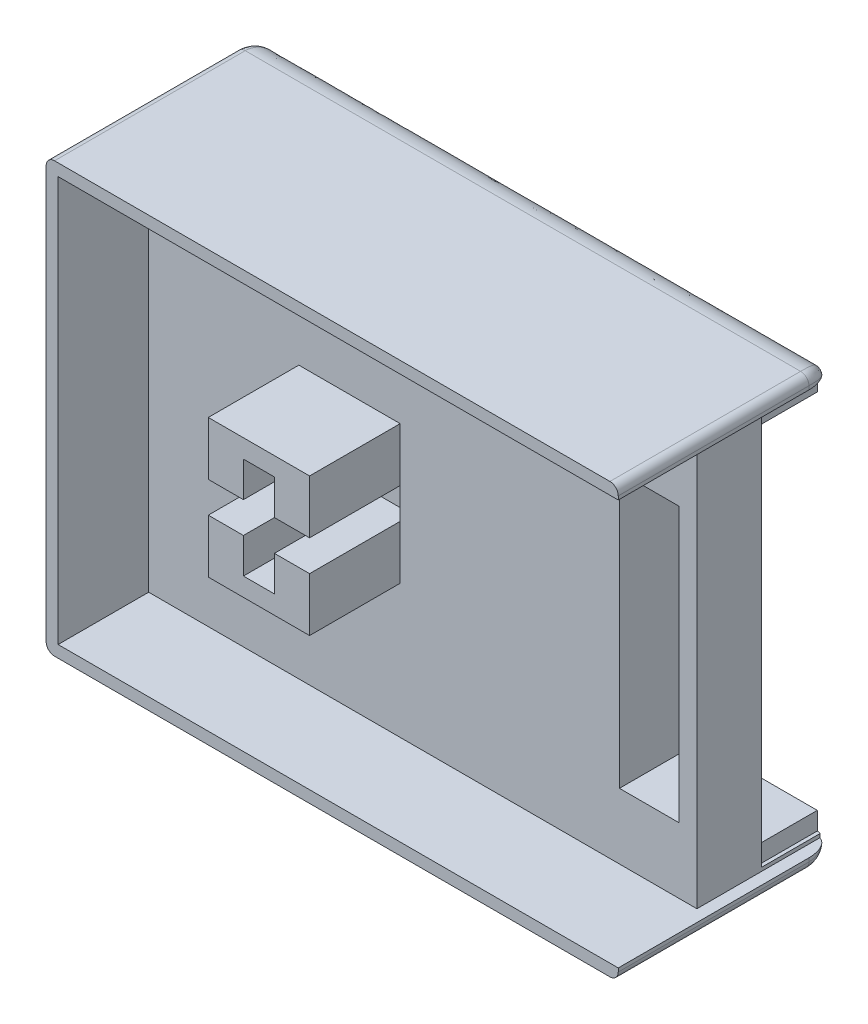
SolidWorks part; units mm, degrees
ref_plane "Front Plane" through (0, 0, 0) normal (0, 0, 1) x (1, 0, 0)
ref_plane "Top Plane" through (0, 0, 0) normal (0, 1, 0) x (1, 0, 0)
ref_plane "Right Plane" through (0, 0, 0) normal (1, 0, 0) x (0, 0, -1)
sketch "Sketch1" plane through (0, 0, 0) normal (0, 0, 1) x (1, 0, 0)
  line L1 (-12, -9) -> (12, -9)
  line L2 (-12, -9) -> (-12, 9)
  line L3 (-12, 9) -> (12, 9)
  line L4 (12, -9) -> (12, 9)
  line L5 (-12, -9) -> (12, 9) construction
  line L6 (-12, 9) -> (12, -9) construction
  point P0 (0, 0)
  dimension "D1" = 24
  dimension "D2" = 18
extrude "Boss-Extrude1" add sketch "Sketch1" along normal blind 13
fillet "Fillet1" radius 0.65 4 edges at (-12, 0, 0) (0, -9, 0) (12, 0, 0) (0, 9, 0) second distance 1 first distance on face at (0, 0, 0)
fillet "Fillet2" radius 0.35 8 edges
sketch "Sketch2" plane through (0, 0, 13) normal (0, 0, 1) x (1, 0, 0)
  line L0 (-11.65, -9) -> (11.65, -9) construction
  line L1 (11.5, 8.5) -> (-11.5, 8.5)
  line L2 (11.5, 8.5) -> (11.5, -8.5)
  line L3 (11.5, -8.5) -> (-11.5, -8.5)
  line L4 (-11.5, 8.5) -> (-11.5, -8.5)
  line L5 (12, -8.65) -> (12, 8.65) construction
  line L6 (11.65, 9) -> (-11.65, 9) construction
  line L7 (-12, 8.65) -> (-12, -8.65) construction
  dimension "D1" = 0.5
  dimension "D2" = 0.5
  dimension "D3" = 0.5
  dimension "D4" = 0.5
extrude "Cut-Extrude1" cut sketch "Sketch2" against normal blind 7.8
sketch "Sketch11" plane through (0, 0, 5.2) normal (0, 0, 1) x (1, 0, 0)
  line L0 (-3.075, 2.9) -> (-3.075, 8.5) construction
  line L1 (-5.2, -2.9) -> (-0.95, -2.9)
  line L2 (-5.2, -2.9) -> (-5.2, 2.9)
  line L3 (-5.2, 2.9) -> (-0.95, 2.9)
  line L4 (-0.95, -2.9) -> (-0.95, 2.9)
  line L5 (-5.2, -2.9) -> (-0.95, 2.9) construction
  line L6 (-5.2, 2.9) -> (-0.95, -2.9) construction
  line L7 (-11.5, 8.5) -> (-11.5, -8.5) construction
  line L8 (11.5, 8.5) -> (-11.5, 8.5) construction
  line L9 (-3.075, -2.9) -> (-3.075, -8.5) construction
  line L10 (-11.5, -8.5) -> (11.5, -8.5) construction
  point P0 (0, 0)
  point P15 (-3.075, 0)
  dimension "D1" = 5.8
  dimension "D2" = 4.25
  dimension "D3" = 6.3
extrude "Boss-Extrude4" add sketch "Sketch11" along normal blind 7.8
sketch "Sketch12" plane through (0, 0, 13) normal (0, 0, 1) x (1, 0, 0)
  line L0 (-5.2, 2.9) -> (-5.2, -2.9) construction
  line L1 (-0.95, 0.65) -> (-5.2, 0.65)
  line L2 (-0.95, 0.65) -> (-0.95, -0.65)
  line L3 (-0.95, -0.65) -> (-5.2, -0.65)
  line L4 (-5.2, 0.65) -> (-5.2, -0.65)
  line L5 (-0.95, 0.65) -> (-5.2, -0.65) construction
  line L6 (-0.95, -0.65) -> (-5.2, 0.65) construction
  line L7 (-0.95, -2.9) -> (-0.95, 2.9) construction
  line L8 (-3.075, 0.65) -> (-3.075, 2.9) construction
  line L9 (-0.95, 2.9) -> (-5.2, 2.9) construction
  line L10 (-3.075, -0.65) -> (-3.075, -2.9) construction
  line L11 (-5.2, -2.9) -> (-0.95, -2.9) construction
  point P0 (-3.075, 0)
  dimension "D1" = 1.3
extrude "Cut-Extrude6" cut sketch "Sketch12" against normal blind 8.3
sketch "Sketch13" plane through (0, 0, 13) normal (0, 0, 1) x (1, 0, 0)
  line L0 (-5.2, 0.65) -> (-5.2, -0.65) construction
  line L1 (-3.725, -2.125) -> (-2.425, -2.125)
  line L2 (-3.725, -2.125) -> (-3.725, 2.125)
  line L3 (-3.725, 2.125) -> (-2.425, 2.125)
  line L4 (-2.425, -2.125) -> (-2.425, 2.125)
  line L5 (-3.725, -2.125) -> (-2.425, 2.125) construction
  line L6 (-3.725, 2.125) -> (-2.425, -2.125) construction
  line L7 (-0.95, 0.65) -> (-5.2, 0.65) construction
  point P0 (-3.075, 0)
extrude "Cut-Extrude7" cut sketch "Sketch13" against normal blind 8.3
sketch "Sketch14" plane through (0, 0, 13) normal (0, 0, 1) x (1, 0, 0)
  line L0 (12, -8.65) -> (12, 8.65) construction
  line L1 (11.5, 8.5) -> (12, 8.5)
  line L2 (11.5, 8.5) -> (11.5, -8.5)
  line L3 (11.5, -8.5) -> (12, -8.5)
  line L4 (12, 8.5) -> (12, -8.5)
extrude "Cut-Extrude8" cut sketch "Sketch14" against normal through all
sketch "Sketch17" plane through (0, 0, 0) normal (0, 0, -1) x (-1, 0, 0)
  line L0 (-11.35, 8.35) -> (-11.35, -8.35) construction
  line L1 (-11.35, 7.6) -> (6.65, 7.6)
  line L2 (-11.35, 7.6) -> (-11.35, -7.6)
  line L3 (-11.35, -7.6) -> (6.65, -7.6)
  line L4 (6.65, 7.6) -> (6.65, -7.6)
  line L5 (0, 7.6) -> (0, 8.35) construction
  line L6 (11.35, 8.35) -> (-11.35, 8.35) construction
  line L7 (0, -7.6) -> (0, -8.35) construction
  line L8 (-11.35, -8.35) -> (11.35, -8.35) construction
  dimension "D1" = 18
  dimension "D2" = 15.2
extrude "Cut-Extrude9" cut sketch "Sketch17" against normal blind 2.5
sketch "Sketch18" plane through (11.35, 0, 0) normal (-1, 0, 0) x (0, 0, 1)
  line L0 (2.5, 7.6) -> (2.5, -7.6) construction
  line L1 (0, 8.35) -> (2.5, 8.35)
  line L2 (0, 8.35) -> (0, -8.35)
  line L3 (0, -8.35) -> (2.5, -8.35)
  line L4 (2.5, 8.35) -> (2.5, -8.35)
extrude "Cut-Extrude10" cut sketch "Sketch18" against normal through all
sketch "Sketch19" plane through (0, 0, 2.5) normal (0, 0, -1) x (-1, 0, 0)
  line L0 (6.65, 7.6) -> (-11.35, 7.6) construction
  line L1 (-10.75, -5.75) -> (-8.25, -5.75)
  line L2 (-10.75, -5.75) -> (-10.75, 5.75)
  line L3 (-10.75, 5.75) -> (-8.25, 5.75)
  line L4 (-8.25, -5.75) -> (-8.25, 5.75)
  line L5 (-10.75, -5.75) -> (-8.25, 5.75) construction
  line L6 (-10.75, 5.75) -> (-8.25, -5.75) construction
  line L7 (-11.35, -7.6) -> (6.65, -7.6) construction
  line L8 (-11.5, -8.35) -> (-11.5, 8.35) construction
  line L9 (-9.5, -5.75) -> (-9.5, -7.6) construction
  line L10 (-9.5674, 5.75) -> (-9.5674, 7.6) construction
  point P0 (-7.9369, 0)
  dimension "D1" = 11.5
  dimension "D3" = 2.5
  dimension "D4" = 0.75
extrude "Cut-Extrude11" cut sketch "Sketch19" against normal through all
sketch "Sketch20" plane through (0, 0, 13) normal (0, 0, 1) x (1, 0, 0)
  line L0 (11.65, 9) -> (-11.65, 9) construction
  line L1 (-12, 8.65) -> (-12, -8.65) construction
  line L2 (-12, 9) -> (12, 9)
  line L3 (-12, 9) -> (-12, -9)
  line L4 (-12, -9) -> (12, -9)
  line L5 (12, 9) -> (12, -9)
  line L6 (-11.65, -9) -> (11.65, -9) construction
  line L7 (12, -8.5) -> (12, 8.5) construction
extrude "Cut-Extrude12" cut sketch "Sketch20" against normal blind 4
sketch "Sketch22" plane through (0, 0, 2.5) normal (0, 0, -1) x (-1, 0, 0)
  line L0 (-10.75, 5.75) -> (-10.75, -5.75) construction
  line L1 (-0.95, -6.7) -> (-6.25, -6.7)
  line L2 (-0.95, -6.7) -> (-0.95, -2.7)
  line L3 (-0.95, -2.7) -> (-6.25, -2.7)
  line L4 (-6.25, -6.7) -> (-6.25, -2.7)
  line L5 (-11.35, -7.6) -> (6.65, -7.6) construction
  line L7 (-6.25, -5.9) -> (-0.95, -5.9) construction
  line L8 (-6.25, -5.9) -> (-6.25, -4.3) construction
  line L9 (-6.25, -4.3) -> (-0.95, -4.3) construction
  line L10 (-0.95, -5.9) -> (-0.95, -4.3) construction
  dimension "D1" = 9.8
  dimension "D2" = 4.5
  dimension "D3" = 4
  dimension "D4" = 0.8
  dimension "D5" = 1.6
  dimension "D6" = 3.3
extrude "Cut-Extrude13" cut sketch "Sketch22" against normal blind 1.15
sketch "Sketch23" plane through (0, 0, 2.5) normal (0, 0, -1) x (-1, 0, 0)
  line L1 (-7.25, 4.6) -> (-1.75, 4.6)
  line L2 (-7.25, 4.6) -> (-7.25, -1.4)
  line L3 (-7.25, -1.4) -> (-1.75, -1.4)
  line L4 (-1.75, 4.6) -> (-1.75, -1.4)
  line L5 (-10.75, 5.75) -> (-10.75, -5.75) construction
  line L6 (6.65, 7.6) -> (-11.35, 7.6) construction
  dimension "D1" = 9
  dimension "D2" = 6
  dimension "D3" = 5.5
  dimension "D4" = 9
extrude "Cut-Extrude14" cut sketch "Sketch23" against normal blind 1
sketch "Sketch24" plane through (0, 0, 2.5) normal (0, 0, -1) x (-1, 0, 0)
  line L0 (-10.75, 5.75) -> (-10.75, -5.75) construction
  line L1 (0.25, -7.6) -> (3.75, -7.6)
  line L2 (0.25, -7.6) -> (0.25, 7.6)
  line L3 (0.25, 7.6) -> (3.75, 7.6)
  line L4 (3.75, -7.6) -> (3.75, 7.6)
  line L5 (-11.35, -7.6) -> (6.65, -7.6) construction
  line L6 (6.65, 7.6) -> (-11.35, 7.6) construction
  dimension "D1" = 14.5
  dimension "D2" = 3.5
  dimension "D3" = 0
  dimension "D4" = 0
extrude "Cut-Extrude15" cut sketch "Sketch24" against normal blind 1.15
